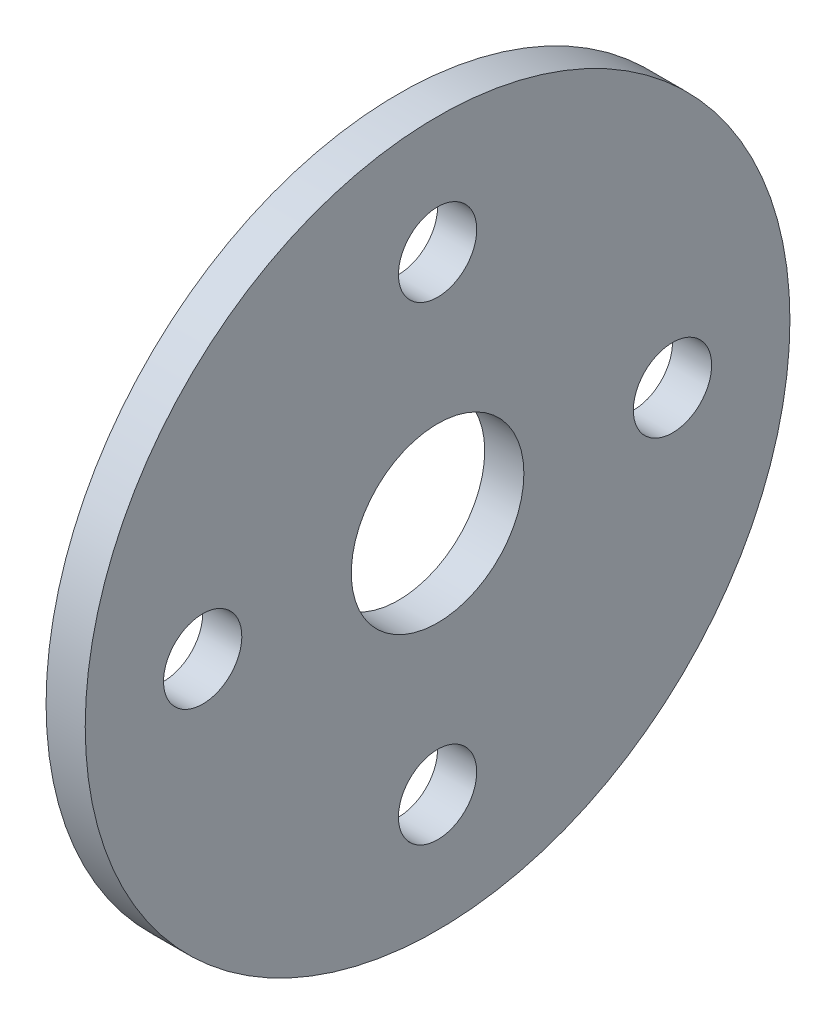
SolidWorks part; units mm, degrees
material "1023 Carbon Steel Sheet (SS)"
ref_plane "Front Plane" through (0, 0, 0) normal (0, 0, 1) x (1, 0, 0)
ref_plane "Top Plane" through (0, 0, 0) normal (0, 1, 0) x (1, 0, 0)
ref_plane "Right Plane" through (0, 0, 0) normal (1, 0, 0) x (0, 0, -1)
sketch "Sketch1" plane through (0, 0, 0) normal (1, 0, 0) x (0, 0, -1)
  circle A0 centre (0, 0) radius 28.575
  circle A1 centre (0, 0) radius 6.999
  circle A2 centre (0, 0) radius 11.1125 construction
  dimension "D1" = 13.9979
  dimension "OD" = 57.15
  dimension "D2" = 22.225
extrude "Boss-Extrude1" add sketch "Sketch1" along normal blind 3.175
sketch "Sketch2" plane through (0, 0, 0) normal (1, 0, 0) x (0, 0, -1)
  line L0 (-28.575, 0) -> (28.575, 0) construction
  circle A0 centre (0, 19.05) radius 3.175
  circle A1 centre (0, 0) radius 28.575 construction
  point P12 (0, 0)
  dimension "D2" = 6.35
  dimension "D1" = 19.05
extrude "Cut-Extrude1" cut sketch "Sketch2" along normal through all
pattern_circular "CirPattern1" count 4 over 360 about axis through (3.175, 0, 0) along (1, 0, 0) of "Cut-Extrude1"
